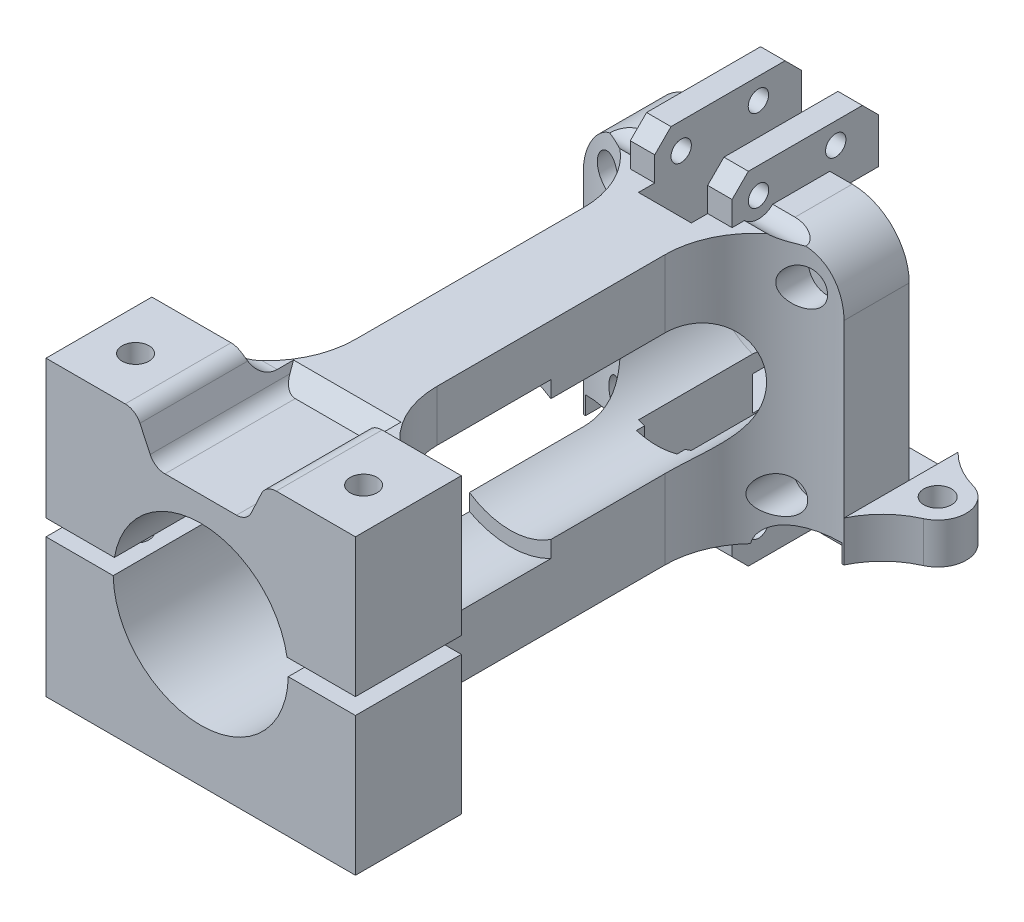
SolidWorks part; units mm, degrees
ref_plane "前视基准面" through (0, 0, 0) normal (0, 0, 1) x (1, 0, 0)
ref_plane "上视基准面" through (0, 0, 0) normal (0, 1, 0) x (1, 0, 0)
ref_plane "右视基准面" through (0, 0, 0) normal (1, 0, 0) x (0, 0, -1)
sketch "草图1" plane through (0, 0, 0) normal (0, 0, 1) x (1, 0, 0)
  line L1 (-16, 16.5) -> (16, 16.5)
  line L2 (-16, 16.5) -> (-16, -16.5)
  line L3 (-16, -16.5) -> (16, -16.5)
  line L4 (16, 16.5) -> (16, -16.5)
  line L5 (-16, 16.5) -> (16, -16.5) construction
  line L6 (-16, -16.5) -> (16, 16.5) construction
  point P0 (0, 0)
  dimension "D1" = 32
  dimension "D2" = 33
extrude "凸台-拉伸1" add sketch "草图1" along normal blind 80
sketch "草图2" plane through (0, 0, 0) normal (0, 0, -1) x (-1, 0, 0)
  line L0 (0, 16.5) -> (0, -16.5) construction
  line L1 (-16, 16.5) -> (16, 16.5) construction
  line L2 (16, -16.5) -> (-16, -16.5) construction
  circle A0 centre (0, 0.7) radius 9
  dimension "D1" = 18
  dimension "D2" = 17.2
extrude "切除-拉伸1" cut sketch "草图2" against normal through all
sketch "草图3" plane through (0, 0, 0) normal (0, 0, -1) x (-1, 0, 0)
  line L1 (-16, -16.5) -> (14.5, -16.5)
  line L2 (-16, -16.5) -> (-16, 15)
  line L3 (-16, 15) -> (14.5, 15)
  line L4 (14.5, -16.5) -> (14.5, 15)
  dimension "D1" = 30.5
  dimension "D2" = 31.5
extrude "切除-拉伸2" cut sketch "草图3" against normal blind 1
sketch "草图4" plane through (0, 0, 1) normal (0, 0, -1) x (-1, 0, 0)
  circle A1 centre (0, 0.7) radius 12.75
  dimension "D1" = 25.5
extrude "切除-拉伸3" cut sketch "草图4" against normal blind 5.1
fillet "圆角1" radius 10.5 1 edges at (-14.5, 15, 0.5)
sketch "草图5" plane through (0, 16.5, 0) normal (0, 1, 0) x (1, 0, 0)
  line L0 (0, 0) -> (0, -80) construction
  line L1 (16, -80) -> (-16, -80) construction
  line L2 (16, -80) -> (16, 0) construction
  line L3 (16, -15) -> (5, -15)
  line L4 (16, -15) -> (16, -65)
  line L5 (16, -65) -> (5, -65)
  line L6 (5, -15) -> (5, -65)
  line L7 (16, 0) -> (-16, 0) construction
  line L8 (-5, -15) -> (-5, -65)
  line L9 (-16, -65) -> (-5, -65)
  line L10 (-16, -15) -> (-16, -65)
  line L11 (-16, -15) -> (-5, -15)
  dimension "D1" = 11
  dimension "D2" = 15
  dimension "D3" = 50
extrude "切除-拉伸4" cut sketch "草图5" against normal through all
fillet "圆角2" radius 11 4 edges at (-5, 12.3417, 65) (-5, 12.3417, 15) (5, 12.3417, 15) (5, 12.3417, 65)
fillet "圆角3" radius 7 2 edges at (-16, 16.5, 7.5) (16, 16.5, 7.5)
sketch "草图6" plane through (0, 0, 80) normal (0, 0, 1) x (1, 0, 0)
  line L1 (-16, -16.5) -> (16, -16.5)
  line L2 (-16, -16.5) -> (-16, 16.5)
  line L3 (-16, 16.5) -> (16, 16.5)
  line L4 (16, -16.5) -> (16, 16.5)
  line L5 (-16, -16.5) -> (16, 16.5) construction
  line L6 (-16, 16.5) -> (16, -16.5) construction
  point P0 (0, 0)
extrude "切除-拉伸5" cut sketch "草图6" against normal blind 2
sketch "草图7" plane through (0, 0, 78) normal (0, 0, 1) x (1, 0, 0)
  circle A1 centre (0, 0.7) radius 10.75
  dimension "D1" = 21.5
extrude "切除-拉伸6" cut sketch "草图7" against normal blind 38
sketch "草图8" plane through (0, -16.5, 0) normal (0, -1, 0) x (1, 0, 0)
  line L0 (0, 78) -> (0, -27.6134) construction
  line L3 (-16, 78) -> (16, 78) construction
  line L4 (16, 78) -> (16, 65) construction
  line L5 (19.5, 75.5) -> (16, 75.5)
  line L6 (19.5, 68.5) -> (16, 68.5)
  line L7 (16, 75.5) -> (16, 68.5)
  line L8 (-16, 75.5) -> (-16, 68.5)
  line L9 (-19.5, 68.5) -> (-16, 68.5)
  line L10 (-19.5, 75.5) -> (-16, 75.5)
  line L11 (19.5, 10.5) -> (16, 10.5)
  line L12 (19.5, 3.5) -> (16, 3.5)
  line L13 (16, 10.5) -> (16, 3.5)
  line L14 (-16, 10.5) -> (-16, 3.5)
  line L15 (-19.5, 3.5) -> (-16, 3.5)
  line L16 (-19.5, 10.5) -> (-16, 10.5)
  circle A0 centre (19.5, 72) radius 1.7
  arc A1 (19.5, 68.5) -> (19.5, 75.5) centre (19.5, 72) ccw
  arc A2 (-19.5, 68.5) -> (-19.5, 75.5) centre (-19.5, 72) cw
  circle A3 centre (-19.5, 72) radius 1.7
  circle A4 centre (19.5, 7) radius 1.7
  arc A5 (19.5, 3.5) -> (19.5, 10.5) centre (19.5, 7) ccw
  arc A6 (-19.5, 3.5) -> (-19.5, 10.5) centre (-19.5, 7) cw
  circle A7 centre (-19.5, 7) radius 1.7
  dimension "D1" = 3.4
  dimension "D2" = 7
  dimension "D3" = 6
  dimension "D4" = 2
extrude "凸台-拉伸2" add sketch "草图8" against normal blind 5
sketch "草图10" plane through (0, -16.5, 0) normal (0, -1, 0) x (1, 0, 0)
  line L0 (0, 78) -> (0, -15.5405) construction
  line L1 (-16, 78) -> (16, 78) construction
  line L3 (-3.25, 21) -> (3.25, 21)
  line L4 (-3.25, 21) -> (-3.25, 1)
  line L5 (-3.25, 1) -> (3.25, 1)
  line L6 (3.25, 21) -> (3.25, 1)
  line L7 (-3.25, 21) -> (3.25, 1) construction
  line L8 (-3.25, 1) -> (3.25, 21) construction
  line L10 (16, 1) -> (-14.5, 1) construction
  point P5 (0, 11)
  dimension "D1" = 6.5
  dimension "D2" = 20
extrude "切除-拉伸7" cut sketch "草图10" against normal blind 7
sketch "草图11" plane through (0, -9.5, 0) normal (0, -1, 0) x (1, 0, 0)
  line L0 (-12.75, 6.1) -> (12.75, 6.1) construction
  line L1 (-2.5, -8.8) -> (2.5, -8.8)
  line L2 (-2.5, -8.8) -> (-2.5, 21)
  line L3 (-2.5, 21) -> (2.5, 21)
  line L4 (2.5, -8.8) -> (2.5, 21)
  line L5 (-2.5, -8.8) -> (2.5, 21) construction
  line L6 (-2.5, 21) -> (2.5, -8.8) construction
  line L7 (3.25, 21) -> (-3.25, 21) construction
  point P0 (0, 6.1)
  dimension "D1" = 5
extrude "切除-拉伸8" cut sketch "草图11" against normal blind 10
sketch "草图12" plane through (0, 0, 21) normal (0, 0, -1) x (-1, 0, 0)
  line L1 (-2.5, -7.1) -> (2.5, -7.1)
  line L2 (-2.5, -7.1) -> (-2.5, -9.5)
  line L3 (-2.5, -9.5) -> (2.5, -9.5)
  line L4 (2.5, -7.1) -> (2.5, -9.5)
  line L5 (-2.5, -7.1) -> (2.5, -9.5) construction
  line L6 (-2.5, -9.5) -> (2.5, -7.1) construction
  arc A0 (-2.5, -7.9458) -> (2.5, -7.9458) centre (0, 0.7) ccw construction
  point P0 (0, -8.3)
extrude "切除-拉伸9" cut sketch "草图12" against normal blind 1
sketch "草图13" plane through (0, -16.5, 0) normal (0, -1, 0) x (1, 0, 0)
  line L0 (0, 21) -> (0, 0) construction
  line L1 (3.25, 1) -> (6.25, 1)
  line L2 (3.25, 1) -> (3.25, 19)
  line L3 (3.25, 19) -> (6.25, 19)
  line L4 (6.25, 1) -> (6.25, 19)
  line L5 (3.25, 21) -> (-3.25, 21) construction
  line L6 (-6.25, 1) -> (-6.25, 19)
  line L7 (-3.25, 19) -> (-6.25, 19)
  line L8 (-3.25, 1) -> (-3.25, 19)
  line L9 (-3.25, 1) -> (-6.25, 1)
  dimension "D1" = 3
  dimension "D2" = 18
extrude "凸台-拉伸3" add sketch "草图13" along normal blind 4
sketch "草图14" plane through (6.25, 0, 0) normal (1, 0, 0) x (0, 0, -1)
  line L2 (-6.1, -9.5) -> (-21, -9.5) construction
  circle A1 centre (-6.269, -17.5) radius 1.25
  circle A2 centre (-15.75, -16.9) radius 1.25
  dimension "D1" = 2.5
  dimension "D2" = 8
  dimension "D3" = 2.5
  dimension "D5" = 7.4
  dimension "D4" = 9.5
extrude "切除-拉伸10" cut sketch "草图14" against normal up to surface (12.5 mm away) up to face at (-6.25, -18.5, 10)
sketch "草图15" plane through (6.25, 0, 0) normal (1, 0, 0) x (0, 0, -1)
  circle A0 centre (-15.75, -16.9) radius 2.75
  circle A1 centre (-6.269, -17.5) radius 2.75
  arc A4 (-16.9343, -16.5) -> (-14.5657, -16.5) centre (-15.75, -16.9) ccw construction
  dimension "D1" = 5.5
  dimension "D2" = 5.5
extrude "切除-拉伸11" cut sketch "草图15" along normal blind 9.5
mirror "镜向1" about plane through (0, 0, 0) normal (1, 0, 0) of "切除-拉伸11"
sketch "草图16" plane through (0, 16.5, 0) normal (0, 1, 0) x (1, 0, 0)
  line L1 (16, -78) -> (-16, -78)
  line L2 (16, -78) -> (16, -65)
  line L3 (16, -65) -> (-16, -65)
  line L4 (-16, -78) -> (-16, -65)
extrude "凸台-拉伸4" add sketch "草图16" along normal blind 3
fillet "圆角4" radius 3 1 edges at (0, 16.5, 65)
ref_plane "基准面1" through (6.5, 0, 0) normal (1, 0, 0) x (0, 0, -1)
fillet "圆角5" radius 10 8 edges at (-16, -14, 3.5) (-16, -14, 10.5) (-16, -14, 68.5) (-16, -14, 75.5) (16, -14, 3.5) (16, -14, 10.5) (16, -14, 68.5) (16, -14, 75.5)
sketch "草图21" plane through (0, 0, 6.1) normal (0, 0, -1) x (-1, 0, 0)
  line L6 (-2.5, -9.5) -> (-2.5, -7.9458)
  line L7 (2.5, -7.9458) -> (2.5, -9.5)
  line L8 (2.5, -9.5) -> (3.25, -9.5)
  line L9 (3.25, -9.5) -> (3.25, -11.6288)
  line L10 (-3.25, -11.6288) -> (-3.25, -9.5)
  line L11 (-3.25, -9.5) -> (-2.5, -9.5)
  line L12 (-2.5, -9.5) -> (-2.5, -7.9458)
  line L13 (2.5, -7.9458) -> (2.5, -9.5)
  line L14 (2.5, -9.5) -> (3.25, -9.5)
  line L15 (3.25, -9.5) -> (3.25, -11.6288)
  line L16 (-3.25, -11.6288) -> (-3.25, -9.5)
  line L17 (-3.25, -9.5) -> (-2.5, -9.5)
  arc A2 (2.5, -7.9458) -> (-2.5, -7.9458) centre (0, 0.7) ccw
  arc A3 (3.25, -11.6288) -> (-3.25, -11.6288) centre (0, 0.7) ccw
  arc A4 (2.5, -7.9458) -> (-2.5, -7.9458) centre (0, 0.7) ccw
  arc A5 (3.25, -11.6288) -> (-3.25, -11.6288) centre (0, 0.7) ccw
  dimension "D1" = 0
extrude "凸台-拉伸5" add sketch "草图21" along normal up to surface (5.1 mm away) contours L12 A4 L13 L14 L15 A5 L16 L17 up to face at (1.7858, -7.4132, 1)
sketch "草图22" plane through (0, 0, 0) normal (0, 0, -1) x (-1, 0, 0)
  line L6 (9, 16.5) -> (-9, 16.5)
  line L7 (-13.3301, 15) -> (4, 15)
  line L8 (14.5, 4.5) -> (14.5, -16.5)
  line L9 (14.5, -16.5) -> (16, -16.5)
  line L10 (16, -16.5) -> (16, -11.5)
  line L11 (16, -11.5) -> (16, 9.5)
  line L12 (9, 16.5) -> (-9, 16.5)
  line L13 (-13.3301, 15) -> (4, 15)
  line L14 (14.5, 4.5) -> (14.5, -16.5)
  line L15 (14.5, -16.5) -> (16, -16.5)
  line L16 (16, -16.5) -> (16, -11.5)
  line L17 (16, -11.5) -> (16, 9.5)
  arc A3 (-9, 16.5) -> (-13.3301, 15) centre (-9, 9.5) ccw
  arc A4 (14.5, 4.5) -> (4, 15) centre (4, 4.5) ccw
  arc A5 (-9, 16.5) -> (-13.3301, 15) centre (-9, 9.5) ccw
  arc A7 (14.5, 4.5) -> (4, 15) centre (4, 4.5) ccw
  arc A9 (16, 9.5) -> (9, 16.5) centre (9, 9.5) ccw
  arc A10 (16, 9.5) -> (9, 16.5) centre (9, 9.5) ccw
  dimension "D1" = 0
extrude "切除-拉伸14" cut sketch "草图22" against normal up to surface (1 mm away) up to face at (1.4099, -7.856, 1)
sketch "草图23" plane through (0, 0, 1) normal (0, 0, -1) x (-1, 0, 0)
  line L0 (-2.5, -8.9825) -> (-2.5, -9.5)
  line L1 (-2.5, -7.9458) -> (-2.5, -9.5) construction
  line L2 (-2.5, -9.5) -> (-16, -9.5)
  line L3 (-16, 9.5) -> (-16, -11.5) construction
  line L4 (2.5, -8.9825) -> (2.5, -9.5)
  line L5 (2.5, -9.5) -> (2.5, -7.9458) construction
  line L6 (2.5, -9.5) -> (16, -9.5)
  line L7 (16, -11.5) -> (16, 9.5) construction
  line L8 (9, 16.5) -> (-9, 16.5) construction
  line L9 (16, -11.5) -> (16, 9.5)
  line L10 (-16, 9.5) -> (-16, -11.5)
  line L11 (9, 16.5) -> (-9, 16.5)
  circle A0 centre (0, 0.7) radius 10
  arc A1 (16, 9.5) -> (9, 16.5) centre (9, 9.5) ccw construction
  arc A2 (-9, 16.5) -> (-16, 9.5) centre (-9, 9.5) ccw construction
  arc A3 (16, 9.5) -> (9, 16.5) centre (9, 9.5) ccw
  arc A4 (-9, 16.5) -> (-16, 9.5) centre (-9, 9.5) ccw
  line M2 (9, 16.5) -> (-9, 16.5)
  arc M3 (-9, 16.5) -> (-16, 9.5) centre (-9, 9.5) ccw
  line M4 (-16, 9.5) -> (-16, -11.5)
  line M10 (-3.25, -9.5) -> (-2.5, -9.5)
  line M11 (-2.5, -9.5) -> (-2.5, -7.9458)
  line M13 (2.5, -7.9458) -> (2.5, -9.5)
  line M14 (2.5, -9.5) -> (3.25, -9.5)
  line M20 (16, -11.5) -> (16, 9.5)
  arc M21 (16, 9.5) -> (9, 16.5) centre (9, 9.5) ccw
  dimension "D1" = 20
extrude "切除-拉伸15" cut sketch "草图23" against normal blind 6 contours A0 L6 L2 M13 M14 M20 M21 M2 M3 M4 M10 M11 region at (2.9123, -9.2412, 1)
sketch "草图24" plane through (0, 0, 1) normal (0, 0, -1) x (-1, 0, 0)
  line L0 (-9.5033, -14) -> (9.5033, -14)
  circle A0 centre (0, 0.7) radius 10
  arc A1 (9.5033, -14) -> (-9.5033, -14) centre (0, 0.7) ccw
  dimension "D1" = 14
extrude "切除-拉伸16" cut sketch "草图24" against normal blind 6
sketch "草图25" plane through (0, 0, 1) normal (0, 0, -1) x (-1, 0, 0)
  line L2 (-2.5, -8.9825) -> (-2.5, -7.9458)
  line L3 (2.5, -7.9458) -> (2.5, -8.9825)
  line L4 (-2.5, -8.9825) -> (-2.5, -7.9458)
  line L5 (2.5, -7.9458) -> (2.5, -8.9825)
  arc A2 (2.5, -8.9825) -> (-2.5, -8.9825) centre (0, 0.7) ccw
  arc A3 (2.5, -7.9458) -> (-2.5, -7.9458) centre (0, 0.7) ccw
  arc A5 (2.5, -7.9458) -> (-2.5, -7.9458) centre (0, 0.7) ccw
  arc A6 (2.5, -8.9825) -> (-2.5, -8.9825) centre (0, 0.7) ccw
  dimension "D1" = 0
extrude "切除-拉伸17" cut sketch "草图25" against normal up to surface (6 mm away) up to face at (0, -4.2126, 7)
sketch "草图27" plane through (0, 0, 7) normal (0, 0, -1) x (-1, 0, 0)
  circle A0 centre (0, 0.7) radius 9
  dimension "D2" = 18
ref_plane "基准面2" through (0, 0, 2) normal (0, 0, -1) x (-1, 0, 0)
sketch "草图28" plane through (0, 0, 2) normal (0, 0, -1) x (-1, 0, 0)
  circle A1 centre (0, 0.7) radius 9.5
  dimension "D2" = 19
sketch "草图29" plane through (0, 0, 7) normal (0, 0, -1) x (-1, 0, 0)
  circle A0 centre (0, 0.7) radius 11
  dimension "D1" = 22
extrude "凸台-拉伸6" add sketch "草图29" along normal blind 5
loft "切除-放样1" cut profiles "草图28", "草图27" connector at (3.5027, 9.5307, 2) connector at (4.8558, 8.2777, 7)
sketch "草图30" plane through (0, 0, 2) normal (0, 0, -1) x (-1, 0, 0)
  line L1 (-2.5, -7.0532) -> (2.5, -7.0532)
  line L2 (-2.5, -7.0532) -> (-2.5, -12.8474)
  line L3 (-2.5, -12.8474) -> (2.5, -12.8474)
  line L4 (2.5, -7.0532) -> (2.5, -12.8474)
  line L5 (-2.5, -7.9458) -> (-2.5, -9.5) construction
  line L6 (2.5, -9.5) -> (2.5, -7.9458) construction
extrude "切除-拉伸18" cut sketch "草图30" against normal up to vertex (20 mm away) up to point (-2.5, -7.9458, 22)
sketch "草图32" plane through (0, -20.5, 0) normal (0, -1, 0) x (1, 0, 0)
  line L1 (-3.25, 21) -> (3.25, 21)
  line L2 (-3.25, 21) -> (-3.25, 1)
  line L3 (-3.25, 1) -> (3.25, 1)
  line L4 (3.25, 21) -> (3.25, 1)
extrude "切除-拉伸20" cut sketch "草图32" against normal through all both and the other way through all
sketch "草图33" plane through (0, 16.5, 0) normal (0, 1, 0) x (1, 0, 0)
  line L0 (-6.25, -1) -> (-3.25, -1) construction
  line L1 (-3.25, -1) -> (-3.25, -19) construction
  line L2 (-3.25, -19) -> (-6.25, -19) construction
  line L3 (-6.25, -19) -> (-6.25, -1) construction
  line L4 (3.25, -19) -> (3.25, -1) construction
  line L5 (3.25, -1) -> (6.25, -1) construction
  line L6 (6.25, -1) -> (6.25, -19) construction
  line L7 (6.25, -19) -> (3.25, -19) construction
  line L8 (-6.25, -1) -> (-3.25, -1)
  line L9 (-3.25, -1) -> (-3.25, -19)
  line L10 (-3.25, -19) -> (-6.25, -19)
  line L11 (-6.25, -19) -> (-6.25, -1)
  line L12 (3.25, -19) -> (3.25, -1)
  line L13 (3.25, -1) -> (6.25, -1)
  line L14 (6.25, -1) -> (6.25, -19)
  line L15 (6.25, -19) -> (3.25, -19)
extrude "凸台-拉伸7" add sketch "草图33" along normal blind 5
sketch "草图35" plane through (0, 0, 7) normal (0, 0, -1) x (-1, 0, 0)
  line L0 (0, 0) -> (31.1425, 0) construction
  line L1 (14.2254, -9.5) -> (16, -9.5) construction
  line L2 (3.25, -14) -> (9.5033, -14) construction
  line L3 (-9.5033, -14) -> (-3.25, -14) construction
  line L4 (-14.2254, -9.5) -> (-16, -9.5) construction
  line L5 (-6.25, 16.5) -> (-3.25, 16.5)
  line L6 (-6.25, 16.5) -> (-9, 16.5) construction
  line L7 (-6.25, 16.5) -> (-9, 16.5)
  line L8 (6.25, 16.5) -> (8.4502, 16.5)
  line L9 (-14.2254, 9.5) -> (-16, 9.5)
  line L10 (-9.5033, 14) -> (-3.25, 14)
  line L11 (3.25, 14) -> (9.5033, 14)
  line L12 (14.2254, 9.5) -> (16, 9.5)
  line L13 (8.4502, 16.5) -> (-8.4502, 16.5) construction
  line L14 (3.25, 16.5) -> (3.25, 9.0927) construction
  line L15 (-3.25, 16.5) -> (-3.25, 11.2089) construction
  line L16 (3.25, 16.5) -> (6.25, 16.5) construction
  line L18 (8.4502, 16.5) -> (-8.4502, 16.5) construction
  line L19 (8.4502, 16.5) -> (3.25, 16.5)
  line L20 (3.25, 16.5) -> (3.25, 9.0927)
  line L21 (-3.25, 16.5) -> (-3.25, 11.2089)
  line L22 (3.25, 16.5) -> (6.25, 16.5)
  line L23 (8.4502, 16.5) -> (9, 16.5)
  line L24 (-6.25, 16.5) -> (-8.4502, 16.5)
  arc A0 (9.5033, -14) -> (14.2254, -9.5) centre (0, 0.7) ccw construction
  arc A4 (-14.2254, 9.5) -> (-9.5033, 14) centre (0, -0.7) cw
  arc A5 (9.5033, 14) -> (14.2254, 9.5) centre (0, -0.7) cw
  arc A6 (16, 9.5) -> (9, 16.5) centre (9, 9.5) ccw construction
  arc A7 (-9, 16.5) -> (-16, 9.5) centre (-9, 9.5) ccw construction
  arc A8 (16, 9.5) -> (9, 16.5) centre (9, 9.5) ccw
  arc A9 (-9, 16.5) -> (-16, 9.5) centre (-9, 9.5) ccw
  line M3 (-3.25, 11.2089) -> (-3.25, 16.5)
  line M4 (-3.25, 16.5) -> (-6.25, 16.5)
  line M5 (-6.25, 16.5) -> (-9, 16.5)
  arc M6 (-9, 16.5) -> (-16, 9.5) centre (-9, 9.5) ccw
extrude "凸台-拉伸8" add sketch "草图35" along normal up to surface (6 mm away) contours L9 A4 L10 L7 M3 M4 M5 M6 | L12 A8 L23 L8 L19 L20 L11 A5 region at (10.2017, 13.9735, 7) region at (-10.2017, 13.9735, 7) up to face at (4.75, 19, 1)
sketch "草图36" plane through (6.25, 0, 0) normal (1, 0, 0) x (0, 0, -1)
  line L0 (-15.75, -16.9) -> (-15.75, 18.3) construction
  line L1 (-6.269, -17.5) -> (-15.75, -16.9) construction
  line L2 (-6.269, -17.5) -> (-6.269, 17.05) construction
  line L3 (0, 0.7) -> (-40.4265, 0.7) construction
  line L4 (-6.269, 18.9) -> (-15.75, 18.3) construction
  line L5 (-26, 8.1833) -> (-26, -6.7833) construction
  circle A1 centre (-15.75, 18.3) radius 1.25
  circle A2 centre (-6.269, 18.9) radius 1.25
  point P16 (-26, 0.7)
  dimension "D1" = 2.5
  dimension "D3" = 2.5
  dimension "D2" = 17.05
extrude "切除-拉伸21" cut sketch "草图36" against normal through all both and the other way through all
sketch "草图37" plane through (6.25, 0, 0) normal (1, 0, 0) x (0, 0, -1)
  circle A0 centre (-15.75, 18.3) radius 2.5
  circle A1 centre (-6.269, 18.9) radius 2.5
  circle A2 centre (-6.269, 18.9) radius 1.25 construction
  dimension "D1" = 5
  dimension "D2" = 5
extrude "切除-拉伸22" cut sketch "草图37" along normal blind 25
mirror "镜向2" about plane through (0, 0, 0) normal (1, 0, 0) of "切除-拉伸22"
chamfer "倒角1" distance 2 angle 45 8 edges at (-4.75, 21.5, 1) (4.75, 21.5, 1) (4.75, 21.5, 19) (-4.75, 21.5, 19) (4.75, -20.5, 19) (-4.75, -20.5, 19) (-4.75, -20.5, 1) (4.75, -20.5, 1)
sketch "草图38" plane through (0, 19.5, 0) normal (0, 1, 0) x (1, 0, 0)
  line L0 (-16, -78) -> (16, -78) construction
  circle A0 centre (-14, -72) radius 1.65
  circle A1 centre (14, -72) radius 1.65
  dimension "D1" = 3.3
  dimension "D2" = 3.3
  dimension "D4" = 14
  dimension "D5" = 6
  dimension "D6" = 6
  dimension "D3" = 14
extrude "切除-拉伸23" cut sketch "草图38" against normal through all both and the other way through all
sketch "草图39" plane through (0, -11.5, 0) normal (0, 1, 0) x (1, 0, 0)
  line L1 (16, -65) -> (16, -78)
  line L2 (16, -65) -> (16, -78)
  line L3 (-16, -78) -> (-16, -65)
  line L4 (-16, -78) -> (-16, -65)
  arc A3 (20.4442, -75.3702) -> (20.735, -68.7251) centre (19.5, -72) ccw
  arc A4 (16, -65) -> (20.735, -68.7251) centre (24.2634, -59.3683) ccw
  arc A5 (20.4442, -75.3702) -> (16, -78) centre (23.1419, -84.9995) ccw
  arc A6 (20.4442, -75.3702) -> (20.735, -68.7251) centre (19.5, -72) ccw
  arc A7 (16, -65) -> (20.735, -68.7251) centre (24.2634, -59.3683) ccw
  arc A8 (20.4442, -75.3702) -> (16, -78) centre (23.1419, -84.9995) ccw
  arc A9 (-20.735, -68.7251) -> (-20.4442, -75.3702) centre (-19.5, -72) ccw
  arc A10 (-16, -78) -> (-20.4442, -75.3702) centre (-23.1419, -84.9995) ccw
  arc A11 (-20.735, -68.7251) -> (-16, -65) centre (-24.2634, -59.3683) ccw
  arc A12 (-20.735, -68.7251) -> (-20.4442, -75.3702) centre (-19.5, -72) ccw
  arc A13 (-16, -78) -> (-20.4442, -75.3702) centre (-23.1419, -84.9995) ccw
  arc A14 (-20.735, -68.7251) -> (-16, -65) centre (-24.2634, -59.3683) ccw
  dimension "D1" = 0
  dimension "D2" = 0
extrude "切除-拉伸24" cut sketch "草图39" against normal blind 10
sketch "草图40" plane through (0, 19.5, 0) normal (0, 1, 0) x (1, 0, 0)
  line L1 (16, -65) -> (19, -65)
  line L2 (16, -65) -> (16, -78)
  line L3 (16, -78) -> (19, -78)
  line L4 (19, -65) -> (19, -78)
  line L5 (-16, -65) -> (-19, -65)
  line L6 (-16, -65) -> (-16, -78)
  line L7 (-16, -78) -> (-19, -78)
  line L8 (-19, -65) -> (-19, -78)
  dimension "D1" = 13
  dimension "D2" = 3
  dimension "D3" = 13
  dimension "D4" = 3
extrude "凸台-拉伸9" add sketch "草图40" against normal up to surface (36 mm away) up to face at (-14, -16.5, 73.65)
sketch "草图41" plane through (19, 0, 0) normal (1, 0, 0) x (0, 0, -1)
  line L1 (-98, 0.5) -> (-58, 0.5)
  line L2 (-98, 0.5) -> (-98, 2.5)
  line L3 (-98, 2.5) -> (-58, 2.5)
  line L4 (-58, 0.5) -> (-58, 2.5)
  line L5 (-98, 0.5) -> (-58, 2.5) construction
  line L6 (-98, 2.5) -> (-58, 0.5) construction
  line L8 (-78, -16.5) -> (-78, 19.5) construction
  point P0 (-78, 1.5)
  dimension "D1" = 2
  dimension "D2" = 40
extrude "切除-拉伸25" cut sketch "草图41" against normal through all
sketch "草图42" plane through (0, 0, 78) normal (0, 0, 1) x (1, 0, 0)
  line L0 (-8, 19.5) -> (-5.6685, 14.5)
  line L1 (-19, 19.5) -> (19, 19.5) construction
  line L2 (-5.6685, 14.5) -> (5.6685, 14.5)
  line L3 (0, 14.5) -> (0, 19.5) construction
  line L4 (8, 19.5) -> (-8, 19.5)
  line L5 (8, 19.5) -> (5.6685, 14.5)
  dimension "D1" = 8
  dimension "D2" = 5
  dimension "D3" = 65
extrude "切除-拉伸26" cut sketch "草图42" against normal up to vertex (16 mm away) up to point (-8.4502, 16.5, 62)
fillet "圆角6" radius 2 4 edges at (-8, 19.5, 71.5) (8, 19.5, 71.5) (5.6685, 14.5, 70) (-5.6685, 14.5, 70)
chamfer "倒角2" distance 2 angle 45 1 edges at (0, 16.5, 62)
sketch "草图45" plane through (0, 0, 7) normal (0, 0, -1) x (-1, 0, 0)
  line L0 (16, 9.5) -> (14.2254, 9.5) construction
  line L1 (-6.25, 16.5) -> (-16, 16.5)
  line L2 (-6.25, 16.5) -> (-6.25, 9.5)
  line L3 (-6.25, 9.5) -> (-16, 9.5)
  line L4 (-16, 16.5) -> (-16, 9.5)
  line L5 (6.25, 16.5) -> (16, 16.5)
  line L6 (6.25, 16.5) -> (6.25, 9.5)
  line L7 (6.25, 9.5) -> (16, 9.5)
  line L8 (16, 16.5) -> (16, 9.5)
  line L10 (-9.5033, -14) -> (-16, -14)
  line L11 (-9.5033, -14) -> (-9.5033, -9.5)
  line L12 (-9.5033, -9.5) -> (-16, -9.5)
  line L13 (-16, -14) -> (-16, -9.5)
  line L14 (9.5033, -14) -> (16, -14)
  line L15 (9.5033, -14) -> (9.5033, -9.5)
  line L16 (9.5033, -9.5) -> (16, -9.5)
  line L17 (16, -14) -> (16, -9.5)
  arc A0 (16, 9.5) -> (9, 16.5) centre (9, 9.5) ccw construction
extrude "切除-拉伸27" cut sketch "草图45" along normal blind 10
sketch "草图46" plane through (0, -16.5, 0) normal (0, -1, 0) x (1, 0, 0)
  line L1 (-16, 1) -> (-20.0776, 1)
  line L2 (-16, 1) -> (-16, 0)
  line L3 (-16, 0) -> (-20.0776, 0)
  line L4 (-20.0776, 1) -> (-20.0776, 0)
extrude "切除-拉伸28" cut sketch "草图46" against normal blind 10
sketch "草图48" plane through (0, 0, 7) normal (0, 0, -1) x (-1, 0, 0)
  circle A0 centre (-9.9632, -11.1737) radius 1.1
  circle A1 centre (-11.8903, 11.4061) radius 1
  circle A2 centre (11.8903, 11.4061) radius 1
  circle A3 centre (9.9632, -11.1737) radius 1.1
extrude "切除-拉伸30" cut sketch "草图48" against normal blind 15
ref_plane "基准面3" through (0, 0, 27) normal (0, 0, -1) x (-1, 0, 0)
sketch "草图49" plane through (0, 0, 27) normal (0, 0, -1) x (-1, 0, 0)
  circle A0 centre (-11.8903, 11.4061) radius 2.25
  circle A1 centre (11.8903, 11.4061) radius 2.25
  circle A2 centre (9.9632, -11.1737) radius 2.25
  circle A3 centre (-9.9632, -11.1737) radius 2.25
  dimension "D1" = 4.5
  dimension "D2" = 4.5
  dimension "D3" = 4.5
  dimension "D4" = 4.5
extrude "切除-拉伸31" cut sketch "草图49" along normal blind 14
